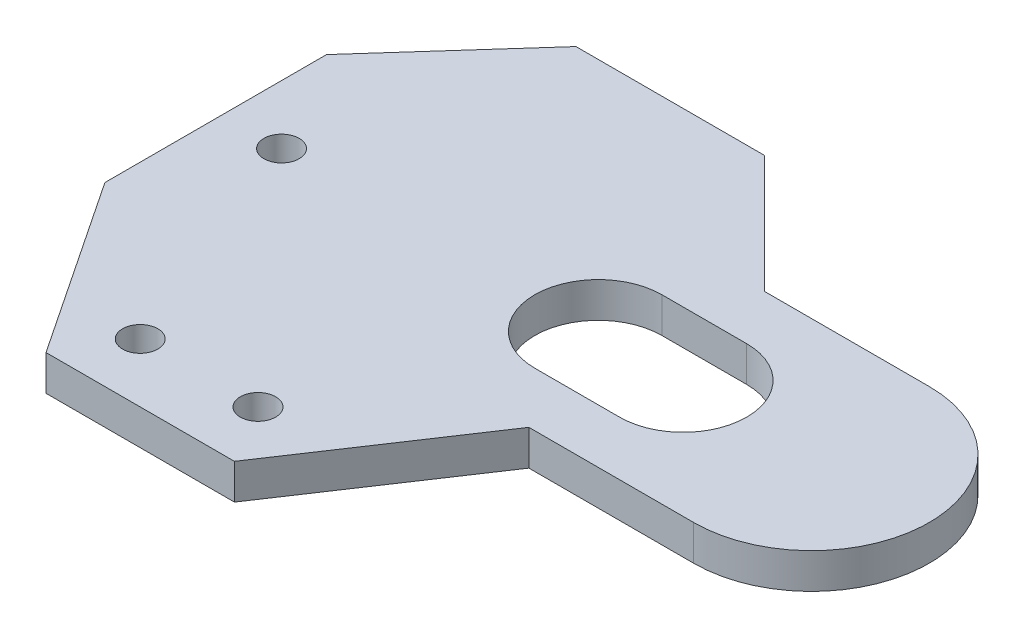
SolidWorks part; units mm, degrees
ref_plane "Front Plane" through (0, 0, 0) normal (0, 0, 1) x (1, 0, 0)
ref_plane "Top Plane" through (0, 0, 0) normal (0, 1, 0) x (1, 0, 0)
ref_plane "Right Plane" through (0, 0, 0) normal (1, 0, 0) x (0, 0, -1)
sketch "Sketch1" plane through (0, 0, 0) normal (0, 1, 0) x (1, 0, 0)
  line L0 (0, 33.8197) -> (10, 45)
  line L1 (0, 0) -> (60, 0)
  line L2 (0, 0) -> (0, 45)
  line L3 (0, 45) -> (60, 45)
  line L4 (60, 0) -> (60, 45)
  line L5 (0, 15) -> (10, 0)
  line L6 (26, 45) -> (36, 35)
  line L7 (26, 0) -> (36, 15)
  line L8 (36, 15) -> (60, 15)
  line L9 (36, 35) -> (60, 35)
  line L10 (60, 25) -> (0, 25) construction
  line L12 (44.5, 19.6) -> (26.5, 19.6)
  line L13 (44.5, 19.6) -> (44.5, 30.4)
  line L14 (44.5, 30.4) -> (26.5, 30.4)
  line L15 (26.5, 19.6) -> (26.5, 30.4)
  circle A0 centre (5, 25) radius 1.5
  circle A1 centre (13, 5) radius 1.5
  circle A2 centre (23, 5) radius 1.5
  dimension "D14" = 3
  dimension "D15" = 10
  dimension "D16" = 3
  dimension "D24" = 3
  dimension "D25" = 3
  dimension "D17" = 3
  dimension "D1" = 45
  dimension "D2" = 60
  dimension "D3" = 15
  dimension "D4" = 10
  dimension "D5" = 10
  dimension "D6" = 15
  dimension "D7" = 16
  dimension "D8" = 16
  dimension "D9" = 10
  dimension "D10" = 10
  dimension "D11" = 10
  dimension "D12" = 20
  dimension "D13" = 10
  dimension "D18" = 5
  dimension "D19" = 5
  dimension "D20" = 4.6
  dimension "D21" = 4.6
  dimension "D22" = 15.5
  dimension "D23" = 18
extrude "Boss-Extrude1" add sketch "Sketch1" along normal blind 3 contours L4 L10 L13 L12 L15 A0 L2 L5 L1 L7 L8 | L10 L4 L9 L6 L3 L0 L2 A0 L15 L14 L13 region at (25.4751, 0, -33.485) region at (24.3362, 0, -14.8271)
fillet "Fillet5" 2 edges at (60, 1.5, -35) (60, 1.5, -15) type full round first side face at (48, 1.5, -35) second side face at (48, 1.5, -15) middle face at (60, 1.5, -25)
fillet "Fillet2" 2 edges at (26.5, 1.5, -19.6) (26.5, 1.5, -30.4) type full round first side face at (35.5, 1.5, -19.6) second side face at (35.5, 1.5, -30.4) middle face at (26.5, 1.5, -25)
fillet "Fillet4" 2 edges at (44.5, 1.5, -30.4) (44.5, 1.5, -19.6) type full round first side face at (38.2, 1.5, -30.4) second side face at (38.2, 1.5, -19.6) middle face at (44.5, 1.5, -25)
